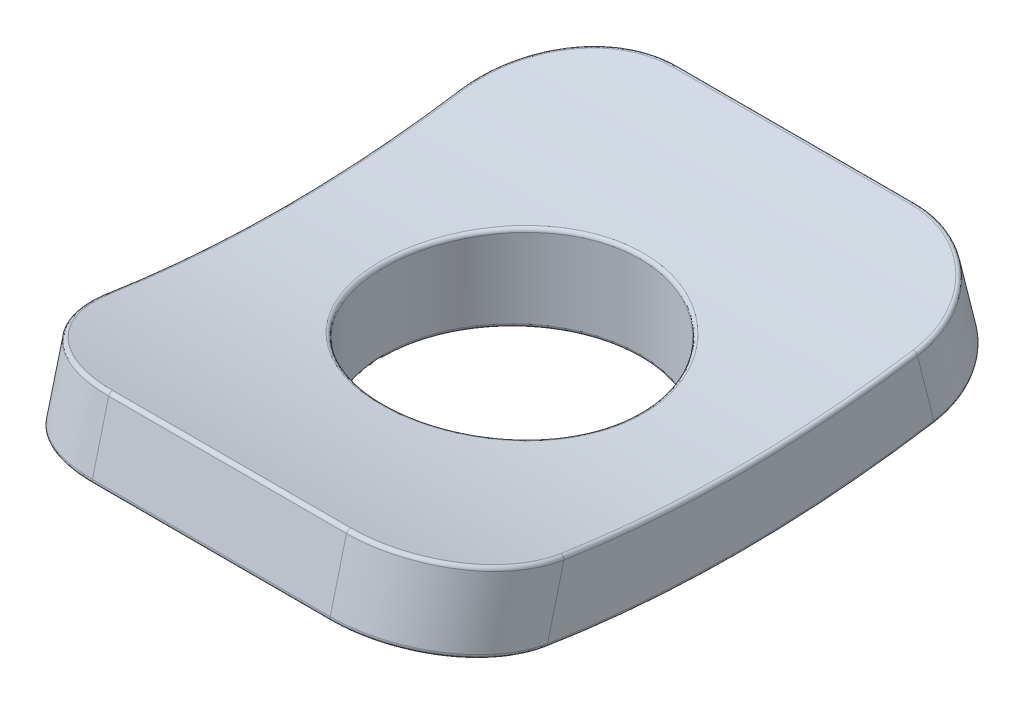
SolidWorks part; units mm, degrees
ref_plane "Front Plane" through (0, 0, 0) normal (0, 0, 1) x (1, 0, 0)
ref_plane "Top Plane" through (0, 0, 0) normal (0, 1, 0) x (1, 0, 0)
ref_plane "Right Plane" through (0, 0, 0) normal (1, 0, 0) x (0, 0, -1)
sketch "Sketch1" plane through (0, 0, 0) normal (1, 0, 0) x (0, 0, -1)
  line L0 (-7.75, 0.9683) -> (-8.2421, -0.9703)
  line L1 (7.75, 0.9683) -> (8.2421, -0.9703)
  arc A0 (-7.75, 0.9683) -> (7.75, 0.9683) centre (0, 31.5) ccw
  arc A1 (-8.2421, -0.9703) -> (8.2421, -0.9703) centre (0, 31.5) ccw
  point P3 (0, 0)
  dimension "D2" = 31.5
  dimension "D1" = 15.5
  dimension "D3" = 2
extrude "Boss-Extrude1" add sketch "Sketch1" along normal mid plane 12.5
fillet "Fillet1" radius 3 4 edges at (-6.25, -0.001, 7.996) (-6.25, -0.001, -7.996) (6.25, -0.001, -7.996) (6.25, -0.001, 7.996)
sketch "Sketch2" plane through (0, 0, 0) normal (0, 1, 0) x (1, 0, 0)
  circle A0 centre (0, 0) radius 3.5
  circle A1 centre (0, 0) radius 6
  dimension "D1" = 12
  dimension "D2" = 7
extrude "Cut-Extrude1" cut sketch "Sketch2" against normal through all both and the other way through all contours A0 region at (0, 0, 0)
extrude "Boss-Extrude2" add sketch "Sketch2<3>" along normal up to body from offset 2.25 separate body contours A1 | A0 offset against normal yes
sketch "Sketch2<3>" plane through (0, 0, 0) normal (0, 1, 0) x (1, 0, 0) same geometry as "Sketch2"
fillet "Fillet2" radius 0.1 19 edges at (0, -2.25, 3.5) (0.7808, 0.1853, -3.4118) (-6.25, 0, 0) (-6.25, -2, 0) (6.25, 0, 0) (6.25, -2, 0) (0, 0.9683, -7.75) (0, -0.9703, 8.2421) (0, 0.9683, 7.75) (5.5952, -1.2296, 7.1429) (5.124, -1.1257, -7.6034) (-5.5952, -1.2296, -7.1429) (-5.124, -1.1257, 7.6034) (5.1239, 0.8132, 7.1112) (5.5956, 0.71, -6.6501) (-5.1239, 0.8132, -7.1112) (-5.5956, 0.71, 6.6501) (0, -2.25, 6) (0, -0.9703, -8.2421)
